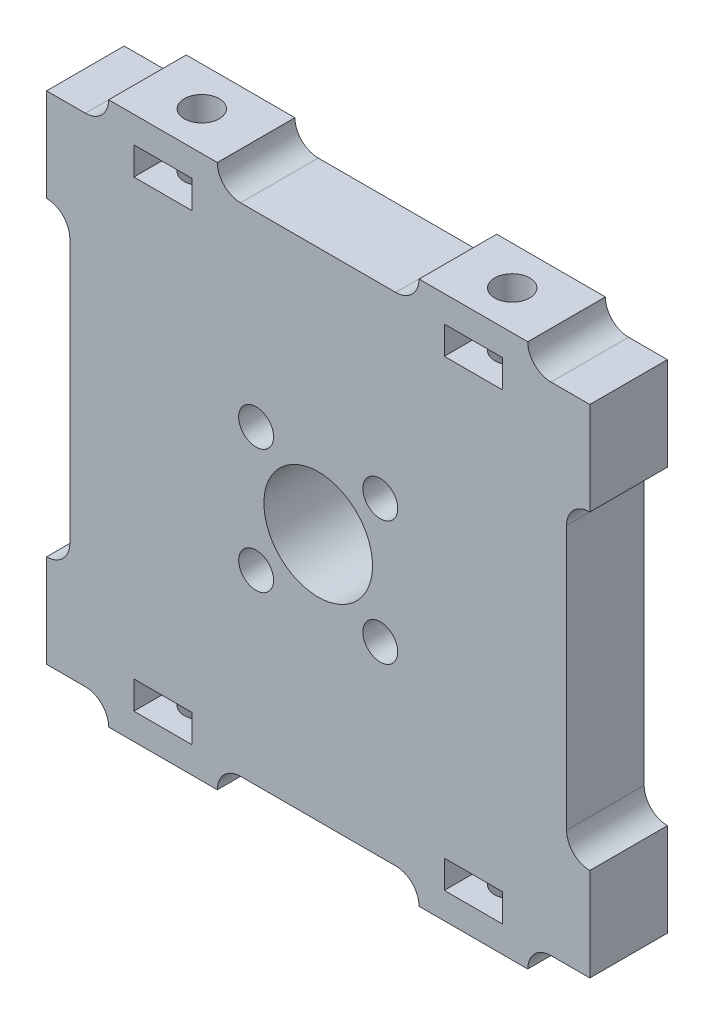
SolidWorks part; units mm, degrees
material "ABS"
ref_plane "Alzado" through (0, 0, 0) normal (0, 0, 1) x (1, 0, 0)
ref_plane "Planta" through (0, 0, 0) normal (0, 1, 0) x (1, 0, 0)
ref_plane "Vista lateral" through (0, 0, 0) normal (1, 0, 0) x (0, 0, -1)
sketch "Croquis1" plane through (0, 0, 0) normal (0, 0, 1) x (1, 0, 0)
  line L1 (-35, -35) -> (35, -35)
  line L2 (-35, -35) -> (-35, 35)
  line L3 (-35, 35) -> (35, 35)
  line L4 (35, -35) -> (35, 35)
  line L5 (-35, -35) -> (35, 35) construction
  line L6 (-35, 35) -> (35, -35) construction
  circle A0 centre (0, 0) radius 7
  point P0 (0, 0)
  dimension "D3" = 14
  dimension "D1" = 70
  dimension "D2" = 70
extrude "Saliente-Extruir1" add sketch "Croquis1" along normal mid plane 10
sketch "Croquis2" plane through (0, 0, 5) normal (0, 0, 1) x (1, 0, 0)
  line L0 (35, 35) -> (-35, 35) construction
  line L1 (13, 32) -> (-13, 32)
  line L2 (13, 32) -> (13, 38)
  line L3 (13, 38) -> (-13, 38)
  line L4 (-13, 32) -> (-13, 38)
  line L5 (13, 32) -> (-13, 38) construction
  line L6 (13, 38) -> (-13, 32) construction
  line L7 (-35, 35) -> (-35, -35) construction
  line L8 (-38, -13) -> (-32, -13)
  line L9 (-38, -13) -> (-38, 13)
  line L10 (-38, 13) -> (-32, 13)
  line L11 (-32, -13) -> (-32, 13)
  line L12 (-38, -13) -> (-32, 13) construction
  line L13 (-38, 13) -> (-32, -13) construction
  line L14 (35, -35) -> (35, 35) construction
  line L15 (32, -13) -> (38, -13)
  line L16 (32, -13) -> (32, 13)
  line L17 (32, 13) -> (38, 13)
  line L18 (38, -13) -> (38, 13)
  line L19 (32, -13) -> (38, 13) construction
  line L20 (32, 13) -> (38, -13) construction
  line L21 (-35, -35) -> (35, -35) construction
  line L22 (13, -32) -> (-13, -32)
  line L23 (13, -32) -> (13, -38)
  line L24 (13, -38) -> (-13, -38)
  line L25 (-13, -32) -> (-13, -38)
  line L26 (13, -32) -> (-13, -38) construction
  line L27 (13, -38) -> (-13, -32) construction
  line L29 (-8, -8) -> (8, -8) construction
  line L30 (-8, -8) -> (-8, 8) construction
  line L31 (-8, 8) -> (8, 8) construction
  line L32 (8, -8) -> (8, 8) construction
  line L33 (-8, -8) -> (8, 8) construction
  line L34 (-8, 8) -> (8, -8) construction
  circle A5 centre (8, 8) radius 2.25
  circle A6 centre (8, -8) radius 2.25
  circle A7 centre (-8, -8) radius 2.25
  circle A8 centre (-8, 8) radius 2.25
  point P0 (0, 35)
  point P7 (-35, 0)
  point P14 (35, 0)
  point P21 (0, -35)
  point P32 (0, 0)
  point P39 (0, 0)
  dimension "D5" = 16
  dimension "D7" = 4.5
  dimension "D1" = 3
  dimension "D2" = 26
  dimension "D6" = 16
extrude "Cortar-Extruir1" cut sketch "Croquis2" against normal through all
sketch "Croquis4" plane through (0, 35, 0) normal (0, 1, 0) x (1, 0, 0)
  line L0 (20, 0) -> (-20, 0) construction
  circle A0 centre (-20, 0) radius 2.25
  circle A1 centre (20, 0) radius 2.25
  point P4 (0, 0)
  dimension "D2" = 4.5
  dimension "D1" = 40
extrude "Cortar-Extruir2" cut sketch "Croquis4" against normal blind 10
ref_plane "Plano1" through (0, 28, 0) normal (0, 1, 0) x (1, 0, 0)
sketch "Croquis5" plane through (0, 28, 0) normal (0, 1, 0) x (1, 0, 0)
  line L0 (-23.75, -2.1651) -> (-23.75, -5)
  line L1 (16.25, 2.1651) -> (16.25, -2.1651)
  line L2 (16.25, -2.1651) -> (20, -4.3301) construction
  line L3 (20, -4.3301) -> (23.75, -2.1651) construction
  line L4 (23.75, -2.1651) -> (23.75, 2.1651)
  line L5 (23.75, 2.1651) -> (20, 4.3301)
  line L6 (20, 4.3301) -> (16.25, 2.1651)
  line L7 (-23.75, 2.1651) -> (-23.75, -2.1651)
  line L8 (-23.75, -2.1651) -> (-20, -4.3301) construction
  line L9 (-20, -4.3301) -> (-16.25, -2.1651) construction
  line L10 (-16.25, -2.1651) -> (-16.25, 2.1651)
  line L11 (-16.25, 2.1651) -> (-20, 4.3301)
  line L12 (-20, 4.3301) -> (-23.75, 2.1651)
  line L13 (-13, -5) -> (-35, -5) construction
  line L14 (-23.75, -5) -> (-16.25, -5)
  line L15 (-16.25, -5) -> (-16.25, -2.1651)
  line L16 (16.25, -2.1651) -> (16.25, -5)
  line L17 (35, -5) -> (13, -5) construction
  line L18 (16.25, -5) -> (23.75, -5)
  line L19 (23.75, -5) -> (23.75, -2.1651)
  circle A0 centre (20, 0) radius 3.75 construction
  circle A1 centre (-20, 0) radius 3.75 construction
  dimension "D1" = 7.5
extrude "Cortar-Extruir3" cut sketch "Croquis5" along normal blind 3.6
mirror "Simetría1" about plane through (0, 0, 0) normal (0, 1, 0) of "Cortar-Extruir2", "Cortar-Extruir3"
sketch "Croquis6" plane through (0, 0, 5) normal (0, 0, 1) x (1, 0, 0)
  line L0 (5.5, 0) -> (-5.5, 0) construction
  line L1 (-35, 35) -> (-27, 35)
  line L2 (-35, 35) -> (-35, 32)
  line L3 (-35, 32) -> (-27, 32)
  line L4 (-27, 35) -> (-27, 32)
  line L5 (35, 35) -> (27, 35)
  line L6 (35, 35) -> (35, 32)
  line L7 (35, 32) -> (27, 32)
  line L8 (27, 35) -> (27, 32)
  line L9 (35, -32) -> (27, -32)
  line L10 (27, -35) -> (27, -32)
  line L11 (35, -35) -> (27, -35)
  line L12 (35, -35) -> (35, -32)
  line L13 (-35, -32) -> (-27, -32)
  line L14 (-27, -35) -> (-27, -32)
  line L15 (-35, -35) -> (-27, -35)
  line L16 (-35, -35) -> (-35, -32)
  line L17 (-35, 13) -> (-35, -13) construction
  line L18 (-32, -13) -> (-32, 13) construction
  line L19 (-38, -20) -> (-32, -20)
  line L20 (-38, -20) -> (-38, 20)
  line L21 (-38, 20) -> (-32, 20)
  line L22 (-32, -20) -> (-32, 20)
  line L23 (-38, -20) -> (-32, 20) construction
  line L24 (-38, 20) -> (-32, -20) construction
  line L25 (0, -5.5) -> (0, 5.5) construction
  line L26 (38, 20) -> (32, 20)
  line L27 (32, -20) -> (32, 20)
  line L28 (38, -20) -> (32, -20)
  line L29 (38, -20) -> (38, 20)
  point P24 (-35, 0)
  dimension "D1" = 8
  dimension "D2" = 3
  dimension "D3" = 40
extrude "Cortar-Extruir4" cut sketch "Croquis6" against normal through all
fillet "Redondeo1" radius 3 12 edges at (27, -32, 0) (13, -32, 0) (-13, -32, 0) (-27, -32, 0) (-32, -20, 0) (-32, 20, 0) (32, -20, 0) (32, 20, 0) (27, 32, 0) (13, 32, 0) (-27, 32, 0) (-13, 32, 0)
